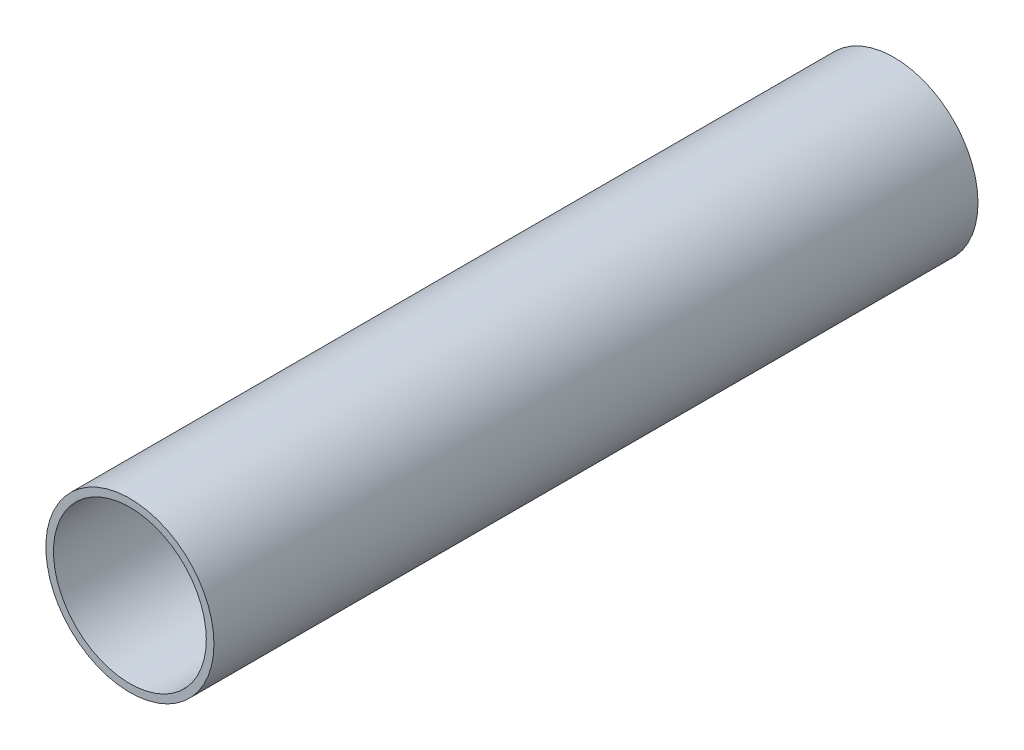
SolidWorks part; units mm, degrees
ref_plane "Front Plane" through (0, 0, 0) normal (0, 0, 1) x (1, 0, 0)
ref_plane "Top Plane" through (0, 0, 0) normal (0, 1, 0) x (1, 0, 0)
ref_plane "Right Plane" through (0, 0, 0) normal (1, 0, 0) x (0, 0, -1)
sketch "Sketch1" plane through (0, 0, 0) normal (0, 0, 1) x (1, 0, 0)
  circle A0 centre (0, 0) radius 5
  circle A1 centre (0, 0) radius 5.5
  dimension "D1" = 10
  dimension "D2" = 11
extrude "Boss-Extrude1" add sketch "Sketch1" along normal blind 25 and the other way blind 25
sketch "Sketch2" plane through (0, 0, 0) normal (0, 0, 1) x (1, 0, 0)
  line L0 (0, 2.8615) -> (0, -6.706) construction
  line L1 (5.9751, -5.9503) -> (0, -5.9503)
  line L2 (0, -5.9503) -> (0, -1.9223)
  spline S0 degree 3 poles (0, -1.9223) (1.113, -1.9563) (2.2045, -4.1934) (4.8352, -5.9503) (5.9751, -5.9503) knots 0 0 0 0 0.401421 1 1 1 1
  point P5 (0, 0)
  point P7 (0, 0)
  point P9 (0, -6.0914)
  point P10 (5.9751, -5.9503)
  point P11 (0, -6.706)
  point P12 (0, 0)
  point P13 (0, -1.9223)
  point P14 (0.8181, -2.1455)
  point P15 (2.2373, -3.675)
revolve "Revolve1" add sketch "Sketch2" angle 360 about L0
sketch "Sketch5" plane through (0, 0, 0) normal (0, 0, 1) x (1, 0, 0)
  circle A0 centre (0, 0) radius 5.5 construction
  circle A1 centre (0, 0) radius 5.5
  circle A2 centre (0, 0) radius 10
  dimension "D1" = 20
extrude "Cut-Extrude1" cut sketch "Sketch5" against normal through all both and the other way through all
